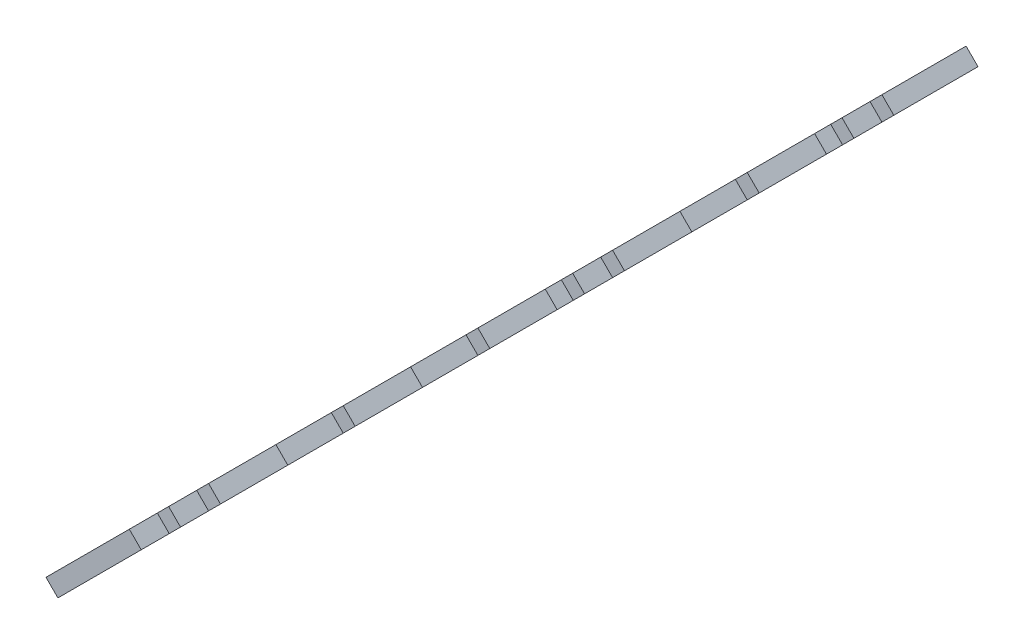
SolidWorks part; units mm, degrees
ref_plane "Front Plane" through (0, 0, 0) normal (0, 0, 1) x (1, 0, 0)
ref_plane "Top Plane" through (0, 0, 0) normal (0, 1, 0) x (1, 0, 0)
ref_plane "Right Plane" through (0, 0, 0) normal (1, 0, 0) x (0, 0, -1)
sketch "Sketch1" plane through (0, 0, 0) normal (0, 0, 1) x (1, 0, 0)
  line L0 (91.6648, 29.3027) -> (52.5461, -9.816) construction
  line L2 (78.5772, 20.7053) -> (74.1015, 16.2295) construction
  line L3 (78.5917, 11.7394) -> (83.0674, 16.2151) construction
  line L4 (39.9621, 9.9289) -> (35.472, 14.4191)
  line L5 (39.9621, 9.9289) -> (71.393, 41.3598)
  line L6 (35.472, 14.4191) -> (66.9029, 45.85)
  line L7 (71.393, 41.3598) -> (66.9029, 45.85)
  line L8 (108.2121, 4.5408) -> (76.7812, -26.8901) construction
  line L9 (76.7812, -26.8901) -> (72.2911, -22.4) construction
  line L10 (103.722, 9.0309) -> (72.2911, -22.4) construction
extrude "Boss-Extrude1" add sketch "Sketch1" along normal up to surface (304.8 mm away)
sketch "Sketch2" plane through (56.3764, 56.3764, 0) normal (0.7071, 0.7071, 0) x (0, 0, -1)
  line L0 (-304.8, -21.2367) -> (0, -21.2367) construction
  line L1 (-279.4, -21.2367) -> (-254, -21.2367)
  line L2 (-279.4, -21.2367) -> (-279.4, -14.8867)
  line L3 (-279.4, -14.8867) -> (-254, -14.8867)
  line L4 (-254, -21.2367) -> (-254, -14.8867)
  line L5 (-304.8, -14.8867) -> (0, -14.8867) construction
  dimension "D1" = 25.4
  dimension "D2" = 25.4
extrude "Boss-Extrude2" add sketch "Sketch2" along normal blind 6.35
pattern_linear "LPattern1" count 6 spacing 50.8 along (0, 0, -1) of "Boss-Extrude2"
sketch "Sketch3" plane through (15.0166, -15.0166, 0) normal (0.7071, -0.7071, 0) x (0, 0, -1)
  circle A0 centre (-273.3375, 57.5033) radius 2.8702
extrude "Cut-Extrude1" cut sketch "Sketch3" against normal up to surface (6.35 mm away) up to face at (66.7302, 45.6773, 155.3308)
sketch "Sketch4" plane through (0, 0, 0) normal (0, 0, -1) x (-1, 0, 0)
  line L0 (-35.472, 14.4191) -> (-39.9621, 9.9289)
  line L1 (-71.393, 50.3401) -> (-35.472, 14.4191) construction
  line L2 (-39.9621, 9.9289) -> (-75.8832, 45.85) construction
  line L3 (-39.9621, 9.9289) -> (-48.9424, 18.9092)
  line L4 (-48.9424, 18.9092) -> (-44.4523, 23.3993)
  line L5 (-44.4523, 23.3993) -> (-35.472, 14.4191)
  dimension "D1" = 12.7
  dimension "D2" = 0
  dimension "D3" = 6.35
extrude "Boss-Extrude3" add sketch "Sketch4" along normal blind 6.35
pattern_linear "LPattern2" count 2 spacing 38.1 along (0.7071, 0.7071, 0) of "Boss-Extrude3"
sketch "Sketch5" plane through (10.5265, -10.5265, 0) normal (-0.7071, 0.7071, 0) x (0.7071, 0.7071, 0)
  line L0 (60.6783, -7.2251) -> (60.6783, -39.5117) construction
  line L1 (47.9783, 6.35) -> (47.9783, 0) construction
  line L2 (73.3783, 6.35) -> (73.3783, 0) construction
  line L3 (73.3783, 0) -> (47.9783, 0) construction
  line B0 (62.8119, 0) -> (58.5447, 0)
  line B1 (58.5447, -11.938) -> (56.2333, -11.938)
  line B2 (56.2333, -11.938) -> (56.2333, -8.763)
  line B3 (56.2333, -8.763) -> (58.5447, -8.763)
  line B4 (58.5447, -8.763) -> (58.5447, 0)
  line B5 (58.5447, -11.938) -> (58.5447, -15.24)
  line B6 (58.5447, -15.24) -> (62.8119, -15.24)
  line B7 (62.8119, -11.938) -> (62.8119, -15.24)
  line B8 (62.8119, -8.763) -> (62.8119, 0)
  line B9 (65.1233, -8.763) -> (62.8119, -8.763)
  line B10 (65.1233, -11.938) -> (65.1233, -8.763)
  line B11 (62.8119, -11.938) -> (65.1233, -11.938)
sketch_block_instance "TSlot-1"
sketch_block "TSlot" parameters "D1"=3.302, "D2"=3.175
extrude "Cut-Extrude2" cut sketch "Sketch5" against normal through all
sketch "Sketch6" plane through (10.5265, -10.5265, 0) normal (-0.7071, 0.7071, 0) x (0.7071, 0.7071, 0)
  line L0 (79.7283, -292.1) -> (47.6349, -292.1) construction
  line L1 (79.7283, -304.8) -> (79.7283, -279.4) construction
  line L2 (79.7283, -139.7) -> (53.7612, -139.7) construction
  line L3 (79.7283, -152.4) -> (79.7283, -127) construction
  line L4 (79.7283, -38.1) -> (53.7612, -38.1) construction
  line L5 (79.7283, -50.8) -> (79.7283, -25.4) construction
  line L6 (86.0783, -25.4) -> (79.7283, -25.4) construction
  line L7 (86.0783, -50.8) -> (79.7283, -50.8) construction
  line L8 (86.0783, -127) -> (79.7283, -127) construction
  line L9 (86.0783, -152.4) -> (79.7283, -152.4) construction
  line L10 (86.0783, -279.4) -> (79.7283, -279.4) construction
  line L11 (35.2783, -304.8) -> (79.7283, -304.8) construction
  line B0 (79.7283, -294.2336) -> (79.7283, -289.9664)
  line B1 (67.7903, -289.9664) -> (67.7903, -287.655)
  line B2 (67.7903, -287.655) -> (70.9653, -287.655)
  line B3 (70.9653, -287.655) -> (70.9653, -289.9664)
  line B4 (70.9653, -289.9664) -> (79.7283, -289.9664)
  line B5 (67.7903, -289.9664) -> (64.4883, -289.9664)
  line B6 (64.4883, -289.9664) -> (64.4883, -294.2336)
  line B7 (67.7903, -294.2336) -> (64.4883, -294.2336)
  line B8 (70.9653, -294.2336) -> (79.7283, -294.2336)
  line B9 (70.9653, -296.545) -> (70.9653, -294.2336)
  line B10 (67.7903, -296.545) -> (70.9653, -296.545)
  line B11 (67.7903, -294.2336) -> (67.7903, -296.545)
  line B12 (79.7283, -141.8336) -> (79.7283, -137.5664)
  line B13 (67.7903, -137.5664) -> (67.7903, -135.255)
  line B14 (67.7903, -135.255) -> (70.9653, -135.255)
  line B15 (70.9653, -135.255) -> (70.9653, -137.5664)
  line B16 (70.9653, -137.5664) -> (79.7283, -137.5664)
  line B17 (67.7903, -137.5664) -> (64.4883, -137.5664)
  line B18 (64.4883, -137.5664) -> (64.4883, -141.8336)
  line B19 (67.7903, -141.8336) -> (64.4883, -141.8336)
  line B20 (70.9653, -141.8336) -> (79.7283, -141.8336)
  line B21 (70.9653, -144.145) -> (70.9653, -141.8336)
  line B22 (67.7903, -144.145) -> (70.9653, -144.145)
  line B23 (67.7903, -141.8336) -> (67.7903, -144.145)
  line B24 (79.7283, -40.2336) -> (79.7283, -35.9664)
  line B25 (67.7903, -35.9664) -> (67.7903, -33.655)
  line B26 (67.7903, -33.655) -> (70.9653, -33.655)
  line B27 (70.9653, -33.655) -> (70.9653, -35.9664)
  line B28 (70.9653, -35.9664) -> (79.7283, -35.9664)
  line B29 (67.7903, -35.9664) -> (64.4883, -35.9664)
  line B30 (64.4883, -35.9664) -> (64.4883, -40.2336)
  line B31 (67.7903, -40.2336) -> (64.4883, -40.2336)
  line B32 (70.9653, -40.2336) -> (79.7283, -40.2336)
  line B33 (70.9653, -42.545) -> (70.9653, -40.2336)
  line B34 (67.7903, -42.545) -> (70.9653, -42.545)
  line B35 (67.7903, -40.2336) -> (67.7903, -42.545)
sketch_block_instance "TSlot-2"
sketch_block_instance "TSlot-3"
sketch_block_instance "TSlot-4"
extrude "Cut-Extrude3" cut sketch "Sketch6" against normal through all
sketch "Sketch7" plane through (15.0166, -15.0166, 0) normal (0.7071, -0.7071, 0) x (-0.7071, -0.7071, 0)
  line L0 (-86.0783, -213.6951) -> (-79.7283, -217.9623) construction
  line L1 (-79.7283, -213.6951) -> (-86.0783, -217.9623) construction
  line L2 (-86.0783, -228.6) -> (-86.0783, -203.2) construction
  line L3 (-86.0783, -217.9623) -> (-79.7283, -217.9623) construction
  line L4 (-86.0783, -65.5623) -> (-79.7283, -61.2951) construction
  line L5 (-86.0783, -65.5623) -> (-79.7283, -65.5623) construction
  line L6 (-86.0783, -76.2) -> (-86.0783, -50.8) construction
  line L7 (-79.7283, -65.5623) -> (-86.0783, -61.2951) construction
  line L8 (-79.7283, -61.2951) -> (-86.0783, -61.2951) construction
  circle A0 centre (-82.9033, -215.8287) radius 2.0955
  circle A1 centre (-82.9033, -63.4287) radius 2.0955
  dimension "D1" = 4.191
extrude "Cut-Extrude4" cut sketch "Sketch7" against normal through all
sketch "Sketch8" plane through (10.5265, -10.5265, 0) normal (-0.7071, 0.7071, 0) x (0.7071, 0.7071, 0)
  line L0 (35.2783, -304.8) -> (35.2783, 6.35) construction
  line L1 (35.2783, -133.35) -> (54.3283, -133.35)
  line L2 (35.2783, -133.35) -> (35.2783, -196.85)
  line L3 (35.2783, -196.85) -> (54.3283, -196.85)
  line L4 (54.3283, -133.35) -> (54.3283, -196.85)
  line L5 (58.5447, 0) -> (47.9783, 0) construction
  dimension "D1" = 133.35
  dimension "D2" = 63.5
  dimension "D3" = 19.05
extrude "Cut-Extrude5" cut sketch "Sketch8" against normal through all
fillet "Fillet1" radius 3.81 4 edges at (51.1875, 25.6444, 196.85) (51.1875, 25.6444, 133.35) (37.7171, 12.174, 196.85) (37.7171, 12.174, 133.35)
